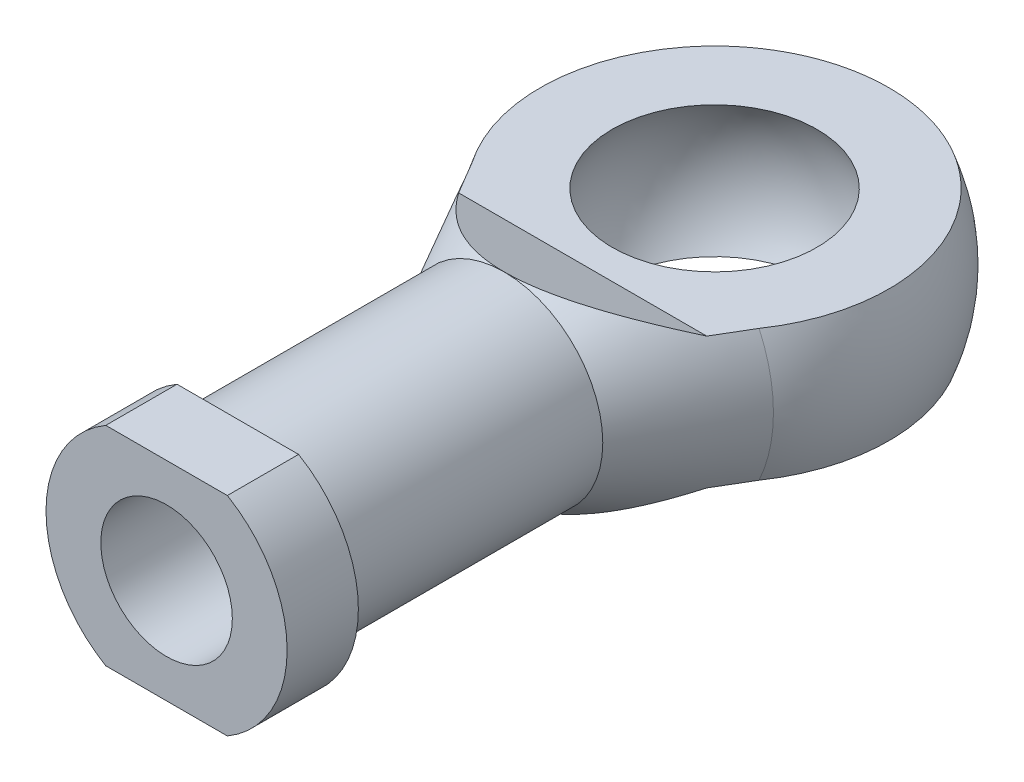
SolidWorks part; units mm, degrees
material "CA"
ref_plane "Płaszczyzna przednia" through (0, 0, 0) normal (0, 0, 1) x (1, 0, 0)
ref_plane "Płaszczyzna górna" through (0, 0, 0) normal (0, 1, 0) x (1, 0, 0)
ref_plane "Płaszczyzna prawa" through (0, 0, 0) normal (1, 0, 0) x (0, 0, -1)
sketch "Szkic1" plane through (0, 0, 0) normal (0, 1, 0) x (1, 0, 0)
  line L0 (0, 17) -> (0, -50)
  line L1 (0, -50) -> (-11, -50)
  line L2 (-11, -50) -> (-11, -43.5)
  line L3 (-11, -43.5) -> (-9, -43.5)
  line L4 (-9, -43.5) -> (-9, -19.2)
  line L5 (-9, -19.2) -> (-14.4022, -9.0319)
  arc A0 (0, 17) -> (-14.4022, -9.0319) centre (0, 0) ccw
  dimension "D6" = 34
  dimension "D1" = 50
  dimension "D2" = 11
  dimension "D3" = 6.5
  dimension "D4" = 2
  dimension "D5" = 24.3
revolve "Obrót1" add sketch "Szkic1" angle 360 about L0
sketch "Szkic2" plane through (0, 0, 0) normal (1, 0, 0) x (0, 0, -1)
  line L0 (-20.3945, 9.5) -> (-12.0329, 6)
  line L1 (-12.0329, 6) -> (29.066, 6)
  line L2 (-20.3945, 9.5) -> (-60.2737, 9.5)
  line L3 (-60.2737, 9.5) -> (-60.2737, 24.4374)
  line L4 (-60.2737, 24.4374) -> (29.066, 24.4374)
  line L5 (29.066, 24.4374) -> (29.066, 6)
  line L6 (0, 0) -> (-50, 0) construction
  line L7 (-50, 11) -> (-50, -11) construction
  line L8 (29.066, -24.4374) -> (29.066, -6)
  line L9 (-60.2737, -24.4374) -> (29.066, -24.4374)
  line L10 (-60.2737, -9.5) -> (-60.2737, -24.4374)
  line L11 (-20.3945, -9.5) -> (-60.2737, -9.5)
  line L12 (-12.0329, -6) -> (29.066, -6)
  line L13 (-20.3945, -9.5) -> (-12.0329, -6)
  dimension "D1" = 6
  dimension "D2" = 9.5
extrude "Wytnij-wyciągnięcie1" cut sketch "Szkic2" against normal through all both and the other way through all contours L4 L5 L1 L0 L2 L3 | L12 L8 L9 L10 L11 L13
sketch "Szkic3" plane through (0, 0, 50) normal (0, 0, 1) x (1, 0, 0)
  circle A0 centre (0, 0) radius 6
  dimension "D1" = 12
extrude "Wytnij-wyciągnięcie2" cut sketch "Szkic3" against normal blind 22 contours A0
sketch "Szkic5" plane through (0, 0, 0) normal (0, 0, 1) x (1, 0, 0)
  line L0 (0, -11.1) -> (0, 11.1)
  arc A0 (0, 11.1) -> (0, -11.1) centre (0, 0) ccw
  dimension "D1" = 22.2
revolve "Wycięcie-obrót1" cut sketch "Szkic5" angle 360 about L0
